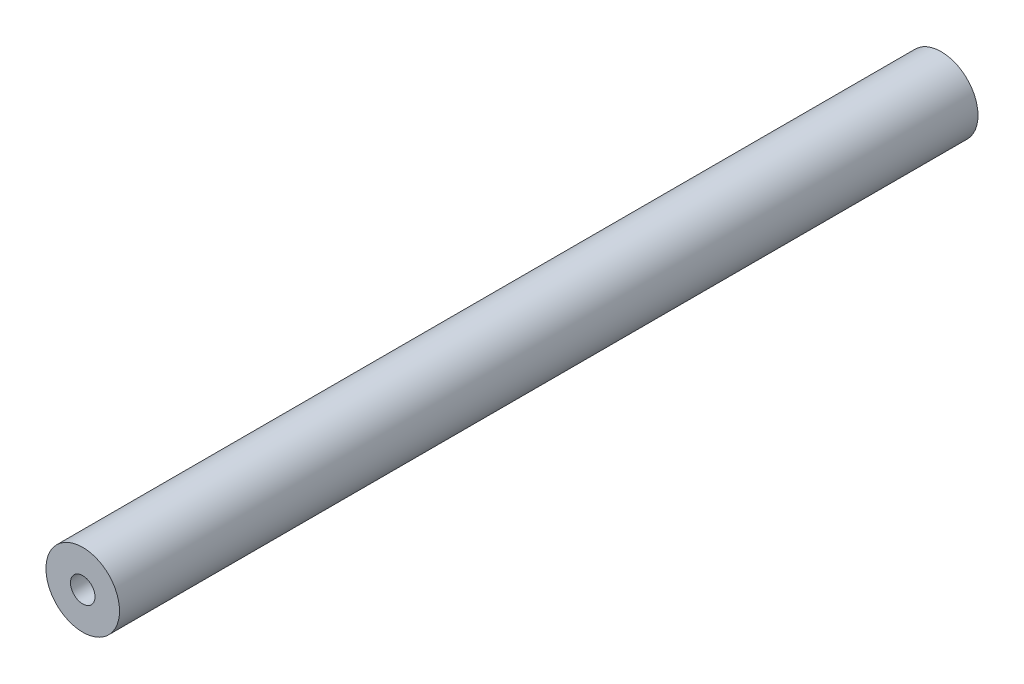
SolidWorks part; units mm, degrees
material "PTFE (general)"
ref_plane "Piano frontale" through (0, 0, 0) normal (0, 0, 1) x (1, 0, 0)
ref_plane "Piano superiore" through (0, 0, 0) normal (0, 1, 0) x (1, 0, 0)
ref_plane "Piano destro" through (0, 0, 0) normal (1, 0, 0) x (0, 0, -1)
sketch "Sketch1" plane through (0, 0, 0) normal (0, 0, 1) x (1, 0, 0)
  circle A0 centre (0, 0) radius 3
  dimension "D1" = 6
extrude "Extrude-Thin1" add sketch "Sketch1" along normal blind 70 thin thin type one direction reverse wall 2
